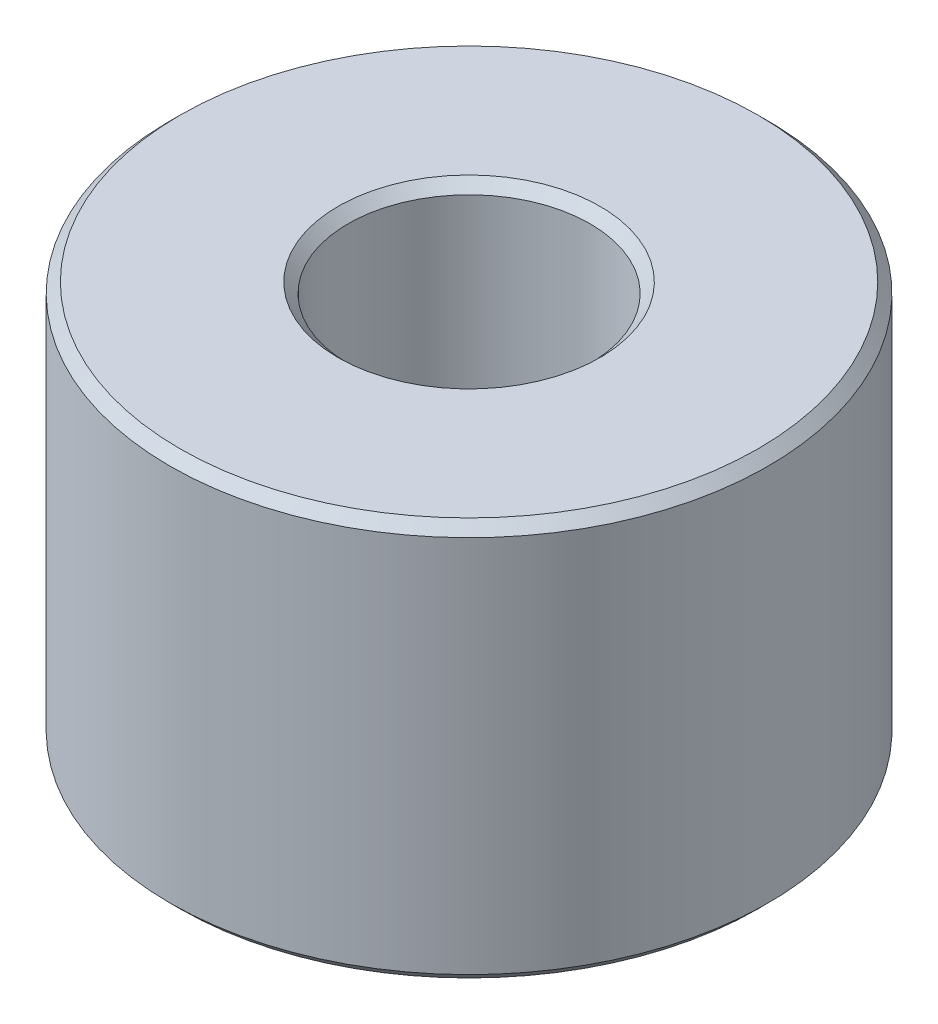
SolidWorks part; units mm, degrees
ref_plane "Front Plane" through (0, 0, 0) normal (0, 0, 1) x (1, 0, 0)
ref_plane "Top Plane" through (0, 0, 0) normal (0, 1, 0) x (1, 0, 0)
ref_plane "Right Plane" through (0, 0, 0) normal (1, 0, 0) x (0, 0, -1)
sketch "Sketch1" plane through (0, 0, 0) normal (0, 1, 0) x (1, 0, 0)
  circle A0 centre (0, 0) radius 30
  dimension "SLEEVE_OD" = 60
extrude "Boss-Extrude1" add sketch "Sketch1" along normal blind 39.9719
sketch "Sketch2" plane through (0, 0, 0) normal (0, 1, 0) x (1, 0, 0)
  circle A0 centre (0, 0) radius 12.1393
  dimension "BORE_D" = 24.2787
extrude "Cut-Extrude1" cut sketch "Sketch2" along normal through all
chamfer "Chamfer1" distance 1.0063 angle 45 4 edges at (0, 39.9719, 12.1393) (0, 0, 12.1393) (0, 0, 30) (0, 39.9719, 30)
